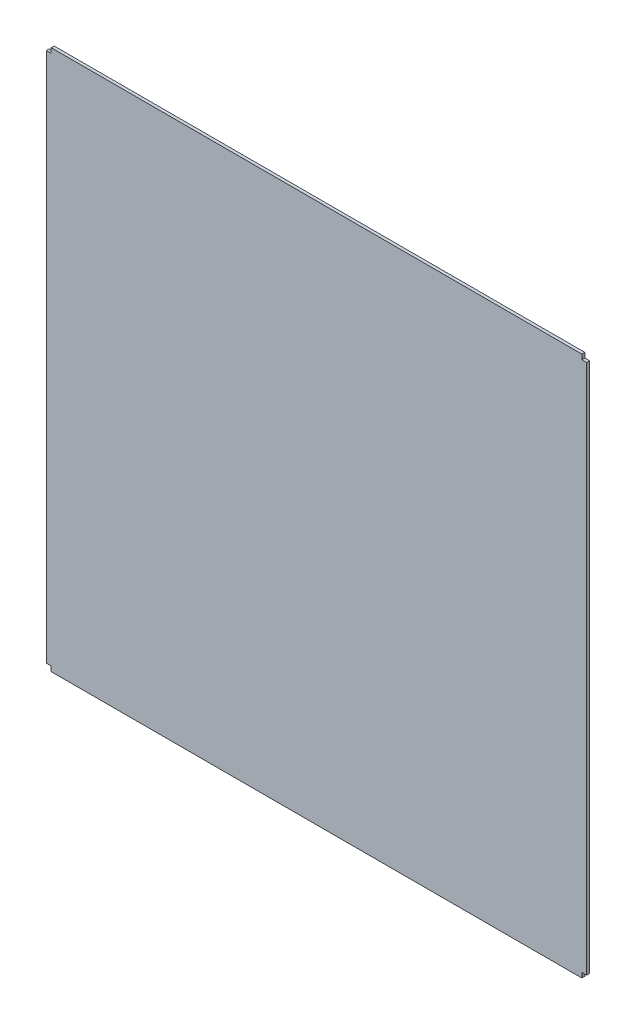
SolidWorks part; units mm, degrees
material "Acrylic (Medium-high impact)"
ref_plane "Front Plane" through (0, 0, 0) normal (0, 0, 1) x (1, 0, 0)
ref_plane "Top Plane" through (0, 0, 0) normal (0, 1, 0) x (1, 0, 0)
ref_plane "Right Plane" through (0, 0, 0) normal (1, 0, 0) x (0, 0, -1)
sketch "Sketch1" plane through (0, 0, 0) normal (0, 0, 1) x (1, 0, 0)
  line L1 (-289.5, -289.5) -> (289.5, -289.5)
  line L2 (-289.5, -289.5) -> (-289.5, 289.5)
  line L3 (-289.5, 289.5) -> (289.5, 289.5)
  line L4 (289.5, -289.5) -> (289.5, 289.5)
  line L5 (-289.5, -289.5) -> (289.5, 289.5) construction
  line L6 (-289.5, 289.5) -> (289.5, -289.5) construction
  point P0 (0, 0)
  dimension "D1" = 579
  dimension "D2" = 579
extrude "Boss-Extrude1" add sketch "Sketch1" along normal mid plane 3.175
sketch "Sketch2" plane through (0, 0, 1.5875) normal (0, 0, 1) x (1, 0, 0)
  line L0 (-284.75, 303.75) -> (-284.75, 285.75) construction
  line L1 (-285.75, 284.75) -> (-303.75, 284.75) construction
  line L2 (284.75, 285.75) -> (284.75, 303.75) construction
  line L3 (303.75, 284.75) -> (285.75, 284.75) construction
  line L4 (285.75, -284.75) -> (303.75, -284.75) construction
  line L5 (284.75, -303.75) -> (284.75, -285.75) construction
  line L6 (-303.75, -284.75) -> (-285.75, -284.75) construction
  line L7 (-284.75, -285.75) -> (-284.75, -303.75) construction
  line L8 (-284.75, 303.75) -> (-284.75, 284.75) construction
  line L9 (-284.75, 284.75) -> (-303.75, 284.75) construction
  line L10 (284.75, 284.75) -> (284.75, 303.75) construction
  line L11 (303.75, 284.75) -> (284.75, 284.75) construction
  line L12 (284.75, -284.75) -> (303.75, -284.75) construction
  line L13 (284.75, -303.75) -> (284.75, -284.75) construction
  line L14 (-303.75, -284.75) -> (-284.75, -284.75) construction
  line L15 (-284.75, -284.75) -> (-284.75, -303.75) construction
  line L16 (-284.25, 303.75) -> (-284.25, 284.25)
  line L17 (-284.25, 284.25) -> (-303.75, 284.25)
  line L18 (-303.75, -284.25) -> (-284.25, -284.25)
  line L19 (-284.25, -284.25) -> (-284.25, -303.75)
  line L20 (284.25, -303.75) -> (284.25, -284.25)
  line L21 (284.25, -284.25) -> (303.75, -284.25)
  line L22 (303.75, 284.25) -> (284.25, 284.25)
  line L23 (284.25, 284.25) -> (284.25, 303.75)
  line L24 (284.25, 303.75) -> (303.75, 284.25)
  line L25 (303.75, -284.25) -> (284.25, -303.75)
  line L26 (-303.75, -284.25) -> (-284.25, -303.75)
  line L27 (-284.25, 303.75) -> (-303.75, 284.25)
  dimension "D1" = 0.5
  dimension "D2" = 0.5
  dimension "D3" = 0.5
  dimension "D4" = 0.5
extrude "Cut-Extrude1" cut sketch "Sketch2" against normal up to surface (3.175 mm away) up to face at (0, 0, -1.5875)
